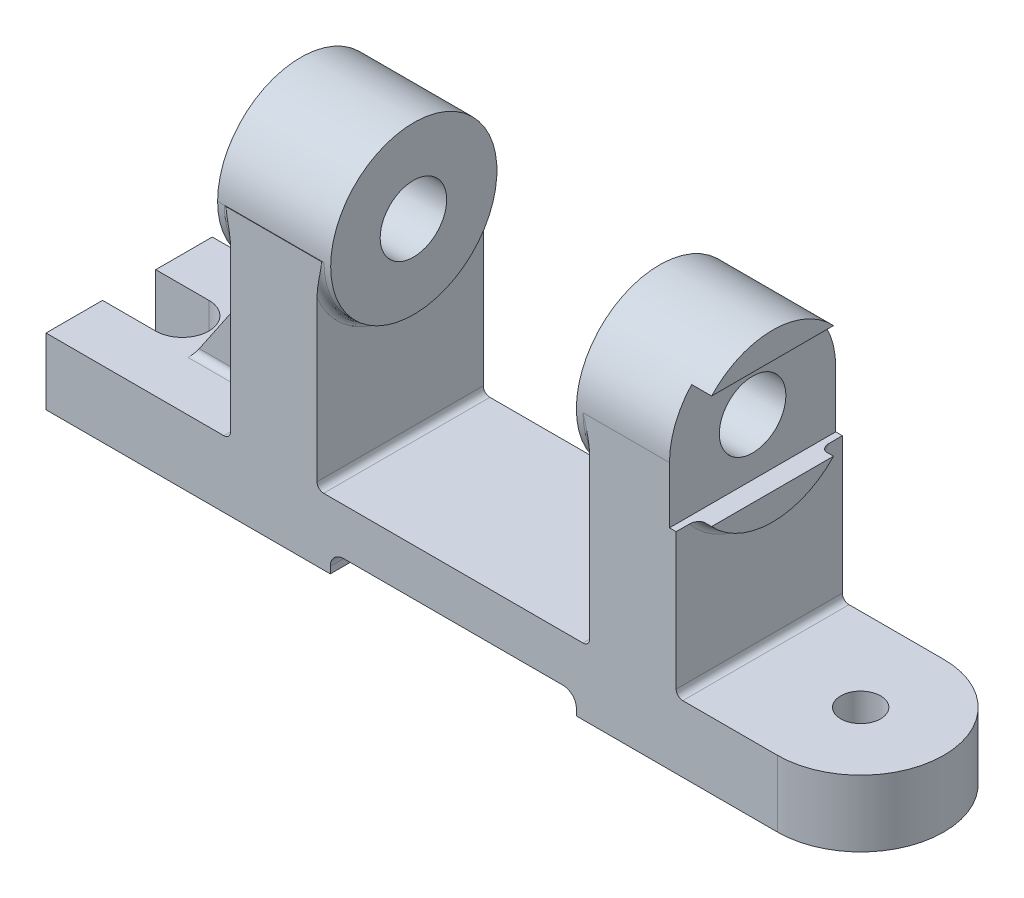
SolidWorks part; units mm, degrees
ref_plane "Front Plane" through (0, 0, 0) normal (0, 0, 1) x (1, 0, 0)
ref_plane "Top Plane" through (0, 0, 0) normal (0, 1, 0) x (1, 0, 0)
ref_plane "Right Plane" through (0, 0, 0) normal (1, 0, 0) x (0, 0, -1)
sketch "Sketch1" plane through (0, 0, 0) normal (0, 1, 0) x (1, 0, 0)
  line L0 (-139.2234, 25.9484) -> (80.7766, 25.9484)
  line L1 (80.7766, -24.0516) -> (-139.2234, -24.0516)
  line L2 (-123.2234, 8.9484) -> (-139.2234, 8.9484)
  line L3 (-139.2234, 8.9484) -> (-139.2234, 25.9484)
  line L4 (80.7766, 0.9484) -> (-148.4751, 0.9484) construction
  line L5 (-139.2234, -24.0516) -> (-139.2234, -7.0516)
  line L6 (-139.2234, -7.0516) -> (-123.2234, -7.0516)
  line L7 (80.7766, 0.9484) -> (147.3912, 0.9484) construction
  arc A0 (80.7766, 25.9484) -> (80.7766, -24.0516) centre (80.7766, 0.9484) cw
  arc A1 (-123.2234, 8.9484) -> (-123.2234, -7.0516) centre (-123.2234, 0.9484) cw
  dimension "D1" = 25
  dimension "D3" = 8
  dimension "D2" = 8
  dimension "D4" = 16
extrude "Boss-Extrude1" add sketch "Sketch1" along normal blind 20
sketch "Sketch3" plane through (0, 0, 24.0516) normal (0, 0, 1) x (1, 0, 0)
  line L0 (-16.7234, -42.4487) -> (-16.7234, 42.4487) construction
  line L1 (-53.7234, 0) -> (-53.7234, 2)
  line L2 (-49.7234, 6) -> (16.2766, 6)
  line L3 (20.2766, 2) -> (20.2766, 0)
  line L4 (-139.2234, 20) -> (80.7766, 20) construction
  line L6 (-139.2234, 20) -> (-139.2234, 0) construction
  line L7 (-53.7234, 0) -> (20.2766, 0)
  arc A0 (20.2766, 2) -> (16.2766, 6) centre (16.2766, 2) ccw
  arc A1 (-53.7234, 2) -> (-49.7234, 6) centre (-49.7234, 2) cw
  point P2 (15.7179, 9.4345)
  dimension "D3" = 4
  dimension "D1" = 37
  dimension "D2" = 74
  dimension "D4" = 14
  dimension "D5" = 122.5
extrude "Cut-Extrude3" cut sketch "Sketch3" against normal through all
sketch "Sketch9" plane through (0, 20, 0) normal (0, 1, 0) x (1, 0, 0)
  point P0 (80.7766, 0.9484)
hole_wizard "M14 Tapped Hole3" positions "3DSketch3" profile "Sketch10" tap size "M14" standard "DIN"
sketch3d "3DSketch3"
  point P0 (80.7766, 20, -0.9484)
sketch "Sketch10" plane through (80.7766, 20, -0.9484) normal (1, 0, 0) x (0, 0, 1)
  line L0 (0, 0) -> (0, 37.6052)
  line L1 (0, 37.6052) -> (6, 34)
  line L2 (6, 34) -> (6, 0)
  line L5 (6, 0) -> (0, 0)
  line L10 (0, 37.6052) -> (-6, 34) construction
  line L11 (0, -6.35) -> (0, 107.95) construction
  dimension "Tap Drill Dia." = 12
  dimension "Tap Drill Depth" = 34
  dimension "Drill Angle" = 118
cosmetic thread "Hole Thread3" parameters "D1"=28, "D2"=14
sketch "Sketch11" plane through (0, 20, 0) normal (0, 1, 0) x (1, 0, 0)
  line L0 (-83.7234, 25.9484) -> (-57.7234, 25.9484)
  line L1 (-83.7234, 25.9484) -> (-83.7234, -24.0516)
  line L2 (-83.7234, -24.0516) -> (-57.7234, -24.0516)
  line L3 (-57.7234, 25.9484) -> (-57.7234, -24.0516)
  line L4 (24.2766, 25.9484) -> (50.2766, 25.9484)
  line L5 (24.2766, 25.9484) -> (24.2766, -24.0516)
  line L6 (24.2766, -24.0516) -> (50.2766, -24.0516)
  line L7 (50.2766, 25.9484) -> (50.2766, -24.0516)
  line L8 (-16.7234, -87.2648) -> (-16.7234, 80.4581) construction
  line L9 (-139.2234, -7.0516) -> (-139.2234, -24.0516) construction
  point P10 (-16.4012, -3.4034)
  dimension "D1" = 26
  dimension "D2" = 26
  dimension "D3" = 41
  dimension "D4" = 82
  dimension "D5" = 122.5
extrude "Boss-Extrude2" add sketch "Sketch11" along normal blind 60 contours L4 L7 L6 L5 | L0 L3 L2 L1
sketch "Sketch12" plane through (-83.7234, 0, 0) normal (-1, 0, 0) x (0, 0, 1)
  circle A0 centre (-1.06, 79.9962) radius 25
extrude "Boss-Extrude3" add sketch "Sketch12" against normal blind 34 from offset 4
sketch "Sketch13" plane through (24.2766, 0, 0) normal (-1, 0, 0) x (0, 0, 1)
  line L1 (-25.9484, 80) -> (24.0516, 80) construction
  circle A0 centre (-0.9484, 80) radius 25
  point P5 (-0.9484, 80)
extrude "Boss-Extrude4" add sketch "Sketch13" against normal blind 34 from offset 4
sketch "Sketch14" plane through (54.2766, 0, 0) normal (1, 0, 0) x (0, 0, -1)
  circle A0 centre (0.9484, 80) radius 10
extrude "Cut-Extrude4" cut sketch "Sketch14" against normal through all both and the other way through all
sketch "Sketch15" plane through (54.2766, 0, 0) normal (1, 0, 0) x (0, 0, -1)
  line L0 (-36.5226, 63) -> (38.4194, 63)
  line L1 (-36.5226, 63) -> (-36.5226, 97)
  line L2 (-36.5226, 97) -> (38.4194, 97)
  line L3 (38.4194, 63) -> (38.4194, 97)
  line L4 (-36.5226, 63) -> (38.4194, 97) construction
  line L5 (-36.5226, 97) -> (38.4194, 63) construction
  point P0 (0.9484, 80)
  dimension "D1" = 34
extrude "Cut-Extrude5" cut sketch "Sketch15" against normal blind 6
ref_plane "Plane1" through (0, 0, -0.9484) normal (0, 0, 1) x (1, 0, 0)
sketch "Sketch16" plane through (0, 0, -0.9484) normal (0, 0, 1) x (1, 0, 0)
  line L0 (-87.7234, 54.9962) -> (-111.4734, 20)
  line L1 (-139.2234, 20) -> (-83.7234, 20) construction
rib "Rib3" sketch "Sketch16" sketch "Sketch16" thickness 16 extrusion direction parallel to sketch draft on no parameters "D1"=16
fillet "Fillet1" radius 2 14 edges at (24.2766, 55, -0.9484) (24.2766, 20, -0.9484) (50.2766, 20, -0.9484) (50.2766, 55, -0.9484) (-57.7234, 55.0242, 0.1228) (-57.7234, 20, -0.9484) (-97.5984, 20, 7.0516) (-83.7234, 64.4296, -20.6222) (-83.7234, 38.1367, -8.9484) (-97.5984, 20, -8.9484) (-83.7234, 20, -17.4484) (-83.7234, 20, 15.5516) (-83.7234, 65.4683, 19.2855) (-83.7234, 38.1744, 7.0516)
